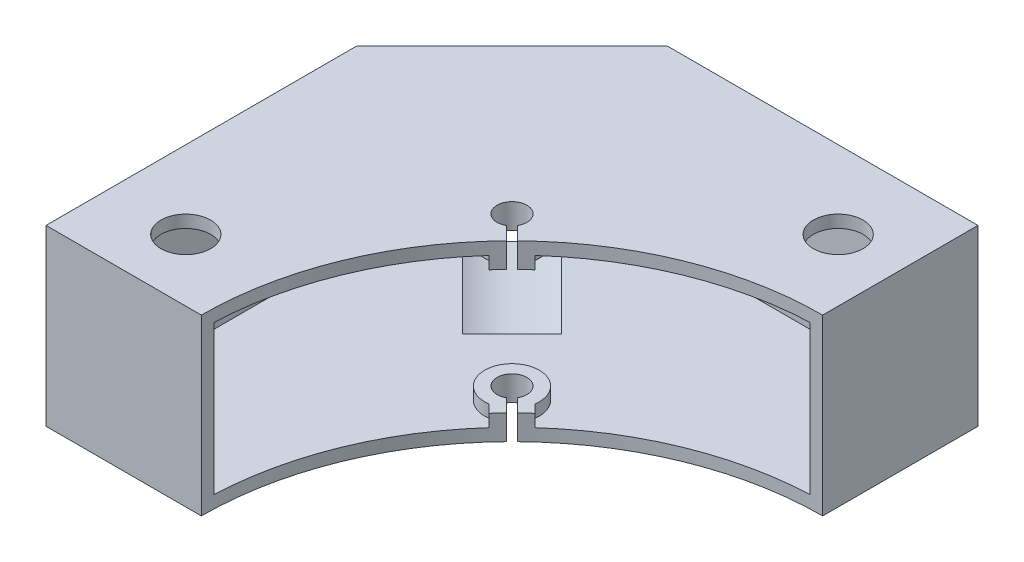
SolidWorks part; units mm, degrees
ref_plane "Front Plane" through (0, 0, 0) normal (0, 0, 1) x (1, 0, 0)
ref_plane "Top Plane" through (0, 0, 0) normal (0, 1, 0) x (1, 0, 0)
ref_plane "Right Plane" through (0, 0, 0) normal (1, 0, 0) x (0, 0, -1)
sketch "Sketch1" plane through (0, 0, 0) normal (0, 1, 0) x (1, 0, 0)
  line L0 (0, 0) -> (0, 50)
  line L1 (0, 0) -> (25, 0)
  line L2 (25, 75) -> (0, 50)
  line L3 (25, 75) -> (75, 75)
  line L4 (75, 75) -> (75, 50)
  line L5 (40.0715, 35.7771) -> (39.2229, 34.9285) construction
  line L6 (39.2229, 34.9285) -> (37.1016, 37.0498)
  line L7 (40.0715, 35.7771) -> (37.9502, 37.8984)
  line L8 (75, 50) -> (75, 0) construction
  line L9 (25, 0) -> (75, 0) construction
  arc A0 (39.2229, 34.9285) -> (25, 0) centre (75, 0) ccw
  arc A1 (40.0715, 35.7771) -> (75, 50) centre (75, 0) cw
  arc A2 (37.1016, 37.0498) -> (37.9502, 37.8984) centre (35.8827, 39.1173) cw
  dimension "D2" = 50
  dimension "D11" = 2.4
  dimension "D5" = 135
  dimension "D6" = 1.2
  dimension "D9" = 3
  dimension "D7" = 25
extrude "Boss-Extrude1" add sketch "Sketch1" along normal blind 28
shell "Shell1" thickness 2 removed face at (56.8395, 14, -44.5982) removed face at (30.4018, 14, -18.1605)
ref_plane "Plane3" through (0, 14, 0) normal (0, 1, 0) x (1, 0, 0)
sketch "Sketch7" plane through (0, 14, 0) normal (0, 1, 0) x (1, 0, 0)
  line L0 (0, 0) -> (0, 50)
  line L1 (0, 0) -> (25, 0)
  line L2 (25, 75) -> (0, 50)
  line L3 (25, 75) -> (75, 75)
  line L4 (75, 75) -> (75, 50)
  line L5 (40.431, 36.1246) -> (38.8754, 34.569) construction
  line L6 (38.8754, 34.569) -> (36.7541, 36.6903)
  line L7 (40.431, 36.1246) -> (38.3097, 38.2459)
  line L8 (75, 50) -> (75, 0) construction
  line L9 (25, 0) -> (75, 0) construction
  arc A0 (38.8754, 34.569) -> (25, 0) centre (75, 0) ccw
  arc A1 (40.431, 36.1246) -> (75, 50) centre (75, 0) cw
  arc A2 (36.7541, 36.6903) -> (38.3097, 38.2459) centre (36.1847, 38.8153) cw
  dimension "D5" = 135
  dimension "D2" = 50
  dimension "D11" = 2.2
  dimension "D6" = 2.2
  dimension "D7" = 25
  dimension "D9" = 3
sketch "Sketch9" plane through (0, 14, 0) normal (0, 1, 0) x (1, 0, 0)
  circle A0 centre (36.1847, 38.8153) radius 6.4
  dimension "D1" = 12.8
extrude "Cut-Extrude1" cut sketch "Sketch9" against normal blind 10 and the other way blind 10
sketch "Sketch11" plane through (-25, 0, -25) normal (-0.7071, 0, -0.7071) x (-0.7071, 0, 0.7071)
  line L0 (-70.7107, 28) -> (-35.3553, 0) construction
  circle A0 centre (-53.033, 14) radius 13.25
  point P8 (-53.033, 14)
  dimension "D1" = 26.5
extrude "Cut-Extrude2" cut sketch "Sketch11" against normal blind 20
ref_plane "Plane4" through (0, 28, 0) normal (0, 1, 0) x (1, 0, 0)
sketch "Sketch12" plane through (0, 28, 0) normal (0, 1, 0) x (1, 0, 0)
  line L5 (40.431, 36.1246) -> (38.8754, 34.569) construction
  line L8 (75, 50) -> (75, 0) construction
  line L9 (25, 0) -> (75, 0) construction
  line L10 (75, 62.5) -> (65, 62.5) construction
  line L11 (12.5, 0) -> (12.5, 10) construction
  circle A3 centre (65, 62.5) radius 4
  circle A4 centre (12.5, 10) radius 4
  dimension "D3" = 8
  dimension "D10" = 8
  dimension "D6" = 2.2
  dimension "D4" = 10
  dimension "D8" = 10
extrude "Cut-Extrude3" cut sketch "Sketch12" against normal blind 2
equation "\"innerRadius\"= 50mm"
equation "\"addedDimension\"= 25mm"
equation "\"D2@Sketch1\"=\"innerRadius\""
equation "\"thinConnectorWidth\" = 1.2mm"
equation "\"D6@Sketch1\"=\"thinConnectorWidth\""
equation "\"D9@Sketch1\"=\"thinConnectorLength\""
equation "\"thinConnectorLength\"= 3mm"
equation "\"connectorCircleRadius\" = 2.4mm"
equation "\"D11@Sketch1\"=\"connectorCircleRadius\""
equation "\"D7@Sketch1\"=\"addedDimension\""
equation "\"shellWidth\"= 2mm"
equation "\"D1@Shell1\"=\"shellWidth\""
equation "\"extrusionHeight\" = 28mm"
equation "\"D1@Boss-Extrude1\"=\"extrusionHeight\""
equation "\"D1@Sketch9\"=2*(\"connectorCircleRadius\"+\"thinConnectorLength\") + \"shellWidth\""
equation "\"D2@Cut-Extrude1\"=\"extrusionHeight\"/2 - \"shellWidth\"*2"
equation "\"D1@Cut-Extrude1\"=\"extrusionHeight\"/2-\"shellWidth\"*2"
equation "\"magnetHoleDiam\" = 26.5mm"
equation "\"D1@Sketch11\" = \"magnetHoleDiam\""
equation "\"throughHoleRadius\"= 4mm"
equation "\"D3@Sketch12\"=\"throughHoleRadius\"*2"
equation "\"D10@Sketch12\"=\"throughHoleRadius\"*2"
equation "\"throughHoleDistanceFromEdge\"= 10mm"
equation "\"D8@Sketch12\"=\"throughHoleDistanceFromEdge\""
equation "\"D1@Cut-Extrude3\"=\"shellWidth\""
